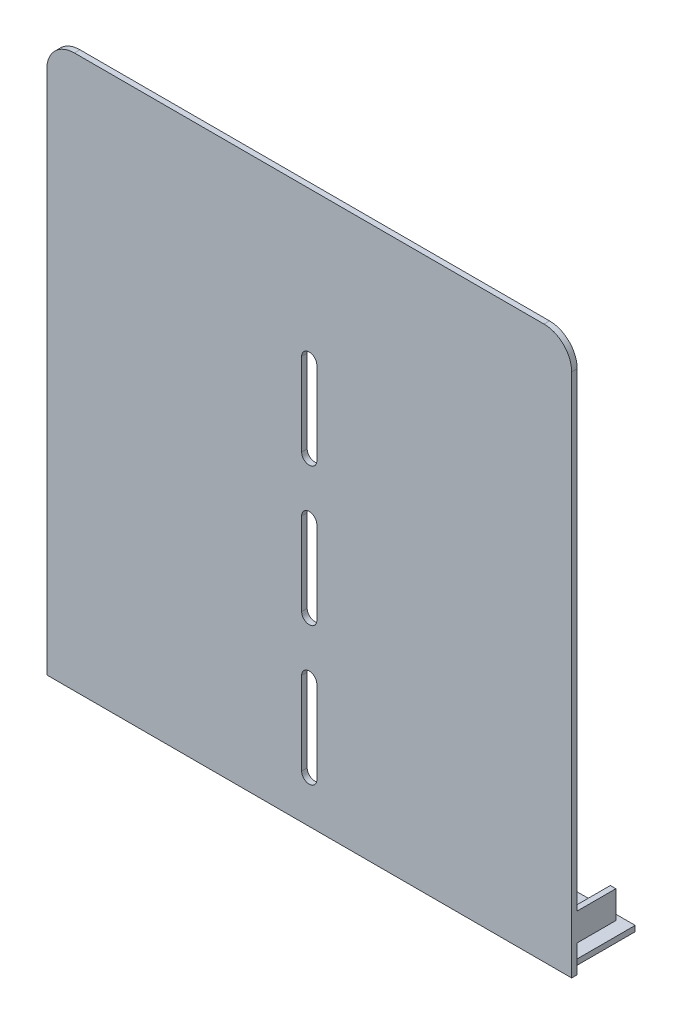
SolidWorks part; units mm, degrees
note: The reader was unsure of these and kept them because the rebuilt part matched: shared geometry of "草图15<3>".
other "标注1"
sketch "草图8" plane through (0, 200, -10) normal (-0.3475, 0.9346, -0.0756) x (0.9188, 0.3555, 0.1714)
other "标注2"
sketch "草图9" plane through (0, 200, -10) normal (-0.3475, 0.9346, -0.0756) x (0.9188, 0.3555, 0.1714)
ref_plane "前视基准面" through (0, 0, 0) normal (0, 0, 1) x (1, 0, 0)
ref_plane "上视基准面" through (0, 0, 0) normal (0, 1, 0) x (1, 0, 0)
ref_plane "右视基准面" through (0, 0, 0) normal (1, 0, 0) x (0, 0, -1)
other "Configuration Table"
sketch "草图1" plane through (0, 0, 0) normal (0, 0, 1) x (1, 0, 0)
  line L0 (0, 0) -> (190, 0)
  line L4 (0, 0) -> (0, 200)
  line L5 (0, 200) -> (190, 200)
  line L6 (190, 200) -> (190, 0)
  dimension "D1" = 190
  dimension "D2" = 200
extrude "凸台-拉伸1" add sketch "草图1" along normal blind 2
sketch "草图2" plane through (0, 0, 0) normal (0, 1, 0) x (1, 0, 0)
  line L0 (95, 0) -> (95, 13.1015)
  line L1 (190, 0) -> (0, 0) construction
  line L2 (3, 0) -> (3, 24)
  line L3 (3, 24) -> (45, 24)
  line L4 (45, 24) -> (45, 0)
  line L5 (45, 0) -> (3, 0)
  line L6 (145, 0) -> (187, 0)
  line L7 (145, 24) -> (145, 0)
  line L8 (187, 24) -> (145, 24)
  line L9 (187, 0) -> (187, 24)
  line L10 (0, -2) -> (0, 0) construction
  line L12 (3, 0) -> (3, 14)
  line L14 (145, 24) -> (145, 14)
  dimension "D1" = 24
  dimension "D2" = 42
  dimension "D3" = 3
  dimension "D4" = 24
extrude "凸台-拉伸2" add sketch "草图2" along normal blind 2
sketch "草图12" plane through (0, 0, 0) normal (1, 0, 0) x (0, 0, -1)
  line L0 (0, 2) -> (0, 10)
  line L2 (0, 0) -> (0, 200) construction
  line L3 (0, 10) -> (14, 10)
  line L4 (14, 10) -> (14, 20)
  line L5 (14, 20) -> (0, 20)
  line L6 (0, 20) -> (0, 10)
  line L7 (0, 0) -> (24, 0) construction
  dimension "D1" = 10
  dimension "D2" = 10
  dimension "D3" = 14
extrude "凸台-拉伸5" add sketch "草图12" along normal blind 2 contours L5 L6 L3 L4
sketch "草图15" plane through (0, 0, 0) normal (1, 0, 0) x (0, 0, -1)
  line L0 (0, 0) -> (0, 120)
  line L1 (0, 0) -> (0, 200) construction
  line L2 (0, 120) -> (0, 135)
  line L3 (0, 135) -> (14, 135)
  line L4 (14, 135) -> (14, 120)
  line L5 (14, 120) -> (0, 120)
  line L6 (14, 120) -> (16, 120)
  line L7 (16, 120) -> (16, 135)
  line L8 (16, 135) -> (14, 135)
  line L9 (0, 0) -> (24, 0) construction
  line L10 (0, 0) -> (0, 100)
  line L11 (0, 100) -> (18.9428, 100)
  line L12 (16, 65) -> (14, 65)
  line L13 (16, 80) -> (16, 65)
  line L14 (14, 80) -> (16, 80)
  line L15 (14, 80) -> (0, 80)
  line L16 (14, 65) -> (14, 80)
  line L17 (0, 65) -> (14, 65)
  line L18 (0, 80) -> (0, 65)
  line L19 (0, 200) -> (0, 80)
  dimension "D1" = 15
  dimension "D2" = 120
  dimension "D3" = 14
  dimension "D4" = 16
extrude "凸台-拉伸9" add sketch "草图15" along normal blind 2 contours L5 L4 L3 L2 | L10 L17 L16 L15
extrude "凸台-拉伸10" add sketch "草图15<3>" along normal up to surface (145 mm away) contours L7 L8 L4 L6 | L16 L12 L13 L14
sketch "草图15<3>" plane through (0, 0, 0) normal (1, 0, 0) x (0, 0, -1) same geometry as "草图15"
sketch "草图17" plane through (0, 0, 0) normal (0, 0, -1) x (-1, 0, 0)
  line L0 (-95, 0) -> (-95, 200)
  line L1 (-45, 0) -> (-145, 0) construction
  line L2 (-190, 200) -> (0, 200) construction
  line L3 (-95, 200) -> (-95, 150)
  line L4 (-95, 150) -> (-95, 146)
  line L5 (-95, 146) -> (-95, 116)
  line L6 (-95, 116) -> (-95, 112)
  line L7 (-95, 146) -> (-95, 116) construction
  line L8 (-92.25, 146) -> (-92.25, 116)
  line L9 (-97.75, 146) -> (-97.75, 116)
  line L10 (-95, 96) -> (-95, 66) construction
  line L11 (-92.25, 96) -> (-92.25, 66)
  line L12 (-97.75, 96) -> (-97.75, 66)
  line L13 (-95, 46) -> (-95, 16) construction
  line L14 (-92.25, 46) -> (-92.25, 16)
  line L15 (-97.75, 46) -> (-97.75, 16)
  arc A0 (-92.25, 146) -> (-97.75, 146) centre (-95, 146) ccw
  arc A1 (-97.75, 116) -> (-92.25, 116) centre (-95, 116) ccw
  arc A2 (-92.25, 96) -> (-97.75, 96) centre (-95, 96) ccw
  arc A3 (-97.75, 66) -> (-92.25, 66) centre (-95, 66) ccw
  arc A4 (-92.25, 46) -> (-97.75, 46) centre (-95, 46) ccw
  arc A5 (-97.75, 16) -> (-92.25, 16) centre (-95, 16) ccw
  point P8 (-95, 131)
  point P18 (-95, 81)
  point P25 (-95, 31)
  dimension "D6" = 5.5
  dimension "D1" = 50
  dimension "D2" = 4
  dimension "D3" = 30
  dimension "D4" = 4
  dimension "D5" = 3
extrude "切除-拉伸1" cut sketch "草图17" against normal blind 20 contours L0 A1 L8 A0 | L9 A1 L0 A0 | L12 A3 L0 A2 | L15 A5 L0 A4 | L0 A5 L14 A4 | L0 A3 L11 A2
fillet "圆角1" radius 10 2 edges at (0, 200, 1) (190, 200, 1)
ref_plane "基准面4" through (95, 0, 0) normal (1, 0, 0) x (0, 0, -1)
mirror "镜向18" about plane through (95, 0, 0) normal (1, 0, 0) of "凸台-拉伸9", "凸台-拉伸10"
mirror "镜向19" about plane through (95, 0, 0) normal (1, 0, 0) of "凸台-拉伸5"
sketch "草图20" plane through (190, 0, 0) normal (1, 0, 0) x (0, 0, -1)
  line L0 (14, 10) -> (14, 20) construction
  line L1 (0, 135) -> (14, 135)
  line L2 (0, 135) -> (0, 10)
  line L3 (0, 10) -> (14, 10)
  line L4 (14, 135) -> (14, 10)
extrude "切除-拉伸4" cut sketch "草图20" against normal blind 10
sketch "草图21" plane through (0, 0, -16) normal (0, 0, -1) x (-1, 0, 0)
  line L0 (-190, 65) -> (0, 65) construction
  line L1 (-190, 135) -> (-45, 135)
  line L2 (-190, 135) -> (-190, 65)
  line L3 (-190, 65) -> (-45, 65)
  line L4 (-45, 135) -> (-45, 65)
  line L5 (0, 120) -> (0, 80) construction
  dimension "D1" = 45
extrude "切除-拉伸5" cut sketch "草图21" against normal blind 2
sketch "草图22" plane through (0, 0, 0) normal (0, 0, -1) x (-1, 0, 0)
  line L0 (-190, 0) -> (-190, 190) construction
  line L1 (-190, 20) -> (-188, 20)
  line L2 (-190, 20) -> (-190, 10)
  line L3 (-190, 10) -> (-188, 10)
  line L4 (-188, 20) -> (-188, 10)
  line L7 (-187, 0) -> (-190, 0) construction
  dimension "D1" = 2
  dimension "D2" = 10
  dimension "D3" = 10
extrude "凸台-拉伸11" add sketch "草图22" along normal blind 14
sketch "草图23" plane through (0, 0, 0) normal (0, -1, 0) x (1, 0, 0)
  line L0 (45, 0) -> (145, 0) construction
  line L1 (55, 0) -> (70, 0)
  line L2 (55, 0) -> (55, -16)
  line L3 (55, -16) -> (70, -16)
  line L4 (70, 0) -> (70, -16)
  line L5 (0, 0) -> (0, -14) construction
  line L6 (120, 0) -> (135, 0)
  line L7 (120, 0) -> (120, -16)
  line L8 (120, -16) -> (135, -16)
  line L9 (135, 0) -> (135, -16)
  line L10 (190, -14) -> (190, 0) construction
  dimension "D1" = 55
  dimension "D2" = 55
  dimension "D3" = 15
  dimension "D4" = 15
  dimension "D5" = 16
  dimension "D6" = 16
extrude "凸台-拉伸12" add sketch "草图23" against normal blind 2
sketch "草图25" plane through (0, 2, 0) normal (0, 1, 0) x (1, 0, 0)
  line L0 (70, 16) -> (70, 0) construction
  line L1 (55, 16) -> (70, 16)
  line L2 (55, 16) -> (55, 14)
  line L3 (55, 14) -> (70, 14)
  line L4 (70, 16) -> (70, 14)
  line L5 (120, 0) -> (120, 16) construction
  line L6 (135, 16) -> (120, 16)
  line L7 (135, 16) -> (135, 14)
  line L8 (135, 14) -> (120, 14)
  line L9 (120, 16) -> (120, 14)
  dimension "D1" = 2
  dimension "D2" = 2
extrude "凸台-拉伸13" add sketch "草图25" along normal blind 43
